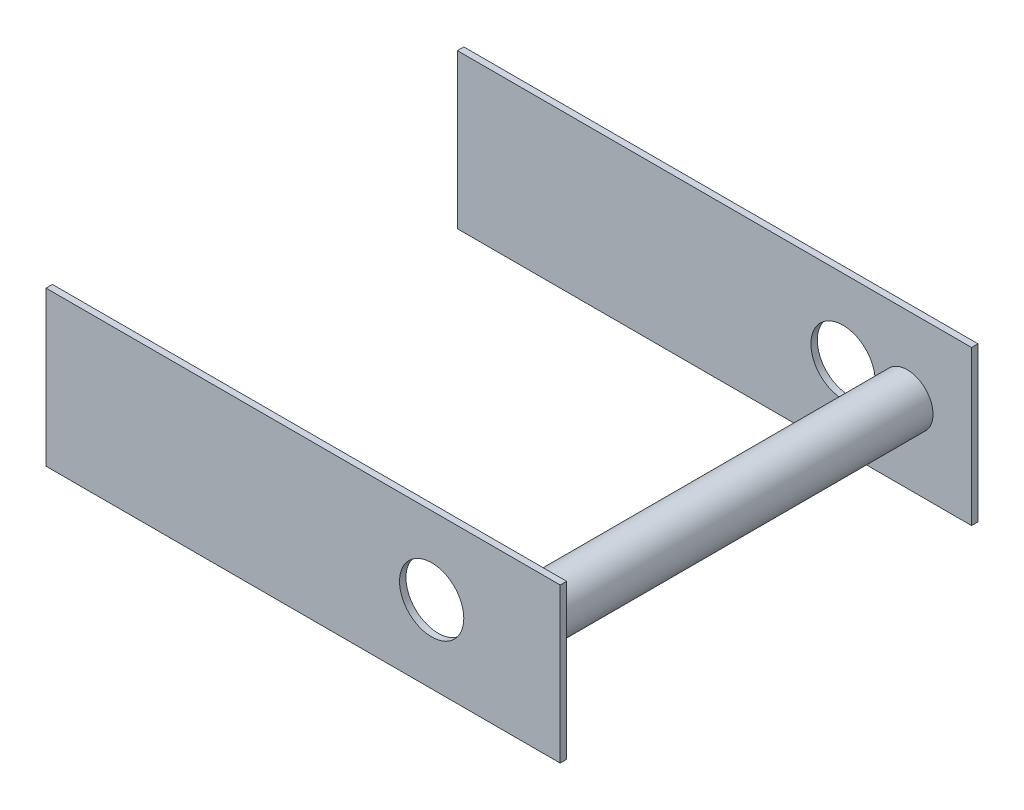
SolidWorks part; units mm, degrees
ref_plane "Front Plane" through (0, 0, 0) normal (0, 0, 1) x (1, 0, 0)
ref_plane "Top Plane" through (0, 0, 0) normal (0, 1, 0) x (1, 0, 0)
ref_plane "Right Plane" through (0, 0, 0) normal (1, 0, 0) x (0, 0, -1)
sketch "Sketch2" plane through (0, 0, 0) normal (0, 0, 1) x (1, 0, 0)
  line L4 (63.5, 38.1) -> (-63.5, 38.1)
  line L5 (63.5, -38.1) -> (63.5, 38.1)
  line L6 (-63.5, -38.1) -> (63.5, -38.1)
  line L7 (-63.5, 38.1) -> (-63.5, -38.1)
  line L8 (63.5, 38.1) -> (-63.5, 38.1)
  line L9 (63.5, -38.1) -> (63.5, 38.1)
  line L10 (-63.5, -38.1) -> (63.5, -38.1)
  line L11 (-63.5, 38.1) -> (-63.5, -38.1)
  circle A1 centre (25.4, 0) radius 12.7
  circle A2 centre (25.4, 0) radius 12.7
  dimension "D1" = 0
  dimension "D2" = 0
sketch "Sketch3" plane through (0, 0, 0) normal (0, 1, 0) x (1, 0, 0)
  line L4 (-63.5, 12.7) -> (-63.5, -25.4)
  line L5 (-63.5, -25.4) -> (63.5, -25.4)
  line L6 (63.5, -25.4) -> (63.5, 0)
  line L7 (-18.5941, 12.7) -> (-63.5, 12.7)
  line L8 (-63.5, 12.7) -> (-63.5, -25.4)
  line L9 (-63.5, -25.4) -> (63.5, -25.4)
  line L10 (63.5, -25.4) -> (63.5, 0)
  line L11 (-18.5941, 12.7) -> (-63.5, 12.7)
  arc A3 (63.5, 0) -> (25.4, 38.1) centre (25.4, 0) ccw
  arc A4 (25.4, 38.1) -> (-7.5956, 19.05) centre (25.4, 0) ccw
  arc A5 (-18.5941, 12.7) -> (-7.5956, 19.05) centre (-18.5941, 25.4) ccw
  arc A6 (63.5, 0) -> (25.4, 38.1) centre (25.4, 0) ccw
  arc A7 (25.4, 38.1) -> (-7.5956, 19.05) centre (25.4, 0) ccw
  arc A8 (-18.5941, 12.7) -> (-7.5956, 19.05) centre (-18.5941, 25.4) ccw
  dimension "D1" = 0
sketch "Sketch6" plane through (0, 0, 0) normal (0, 1, 0) x (1, 0, 0)
  line L0 (25.4, 88.9) -> (25.4, -76.2) construction
  line L1 (25.4, 88.9) -> (25.4, -76.2)
sketch "Sketch4" plane through (0, 0, 0) normal (0, 0, 1) x (1, 0, 0)
  circle A0 centre (25.4, 0) radius 12.7 construction
  circle A1 centre (25.4, 0) radius 12.7 construction
  circle A2 centre (25.4, 0) radius 10.16
  dimension "D1" = 2.54
extrude "Boss-Extrude1" add sketch "Sketch4" along normal up to vertex (76.2 mm away) and the other way up to vertex (88.9 mm away) up to point (25.4, 0, 76.2) other way up to point (25.4, 0, -88.9)
sketch "Sketch7" plane through (0, 0, -88.9) normal (0, 0, -1) x (-1, 0, 0)
  line L0 (152.4, 30.48) -> (152.4, -30.48) construction
  line L1 (-50.8, -30.48) -> (152.4, -30.48)
  line L2 (-50.8, -30.48) -> (-50.8, 30.48)
  line L3 (-50.8, 30.48) -> (152.4, 30.48)
  line L4 (152.4, -30.48) -> (152.4, 30.48)
  line L5 (152.4, -30.48) -> (63.5, -30.48) construction
  dimension "D1" = 25.4
extrude "Boss-Extrude2" add sketch "Sketch7" against normal blind 2.54
sketch "Sketch8" plane through (0, 0, 76.2) normal (0, 0, 1) x (1, 0, 0)
  line L4 (50.8, -30.48) -> (50.8, 30.48)
  line L5 (50.8, 30.48) -> (-152.4, 30.48)
  line L6 (-152.4, 30.48) -> (-152.4, -30.48)
  line L7 (-152.4, -30.48) -> (50.8, -30.48)
  line L8 (50.8, -30.48) -> (50.8, 30.48)
  line L9 (50.8, 30.48) -> (-152.4, 30.48)
  line L10 (-152.4, 30.48) -> (-152.4, -30.48)
  line L11 (-152.4, -30.48) -> (50.8, -30.48)
  dimension "D1" = 0
extrude "Boss-Extrude3" add sketch "Sketch8" against normal blind 2.54
sketch "Sketch9" plane through (0, 0, 76.2) normal (0, 0, 1) x (1, 0, 0)
  line L0 (-152.4, 0) -> (0, 0) construction
  line L1 (-152.4, 30.48) -> (-152.4, -30.48) construction
  circle A0 centre (0, 0) radius 12.7
  dimension "D1" = 25.4
  dimension "D2" = 152.4
extrude "Cut-Extrude1" cut sketch "Sketch9" against normal through all
